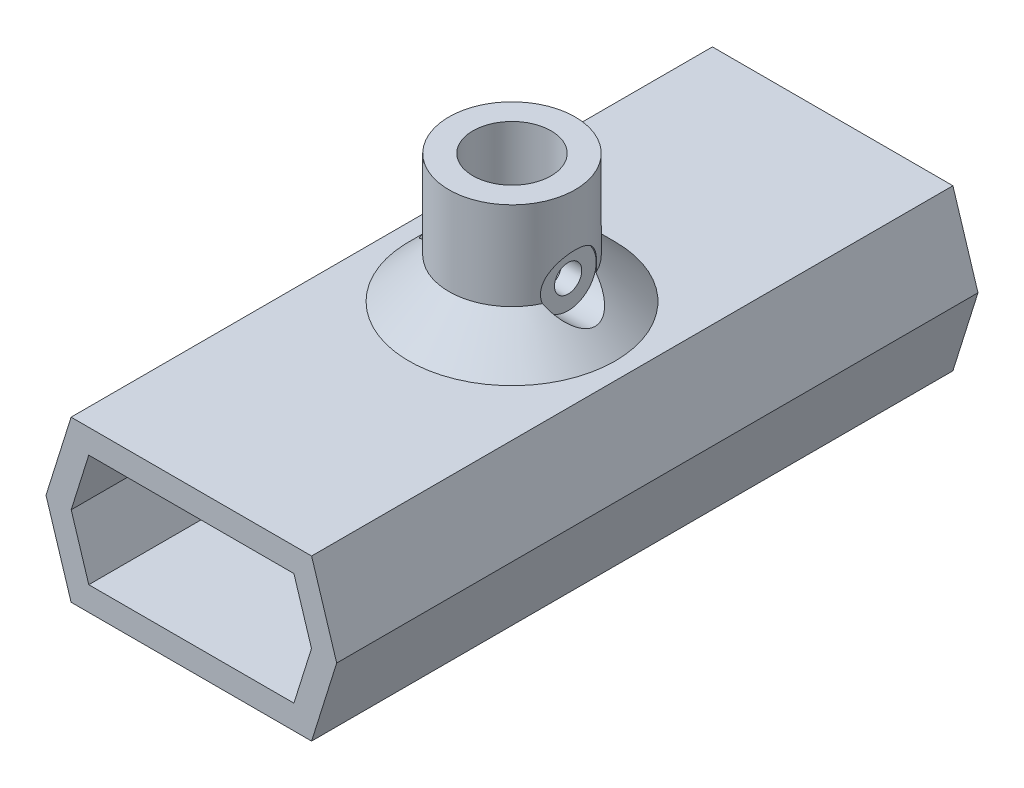
SolidWorks part; units mm, degrees
ref_plane "前视基准面" through (0, 0, 0) normal (0, 0, 1) x (1, 0, 0)
ref_plane "上视基准面" through (0, 0, 0) normal (0, 1, 0) x (1, 0, 0)
ref_plane "右视基准面" through (0, 0, 0) normal (1, 0, 0) x (0, 0, -1)
sketch "草图1" plane through (0, 0, 0) normal (0, 0, 1) x (1, 0, 0)
  line L0 (-15, 0) -> (15, 0)
  line L1 (15, 0) -> (18.1304, -10)
  line L2 (18.1304, -10) -> (15, -20)
  line L3 (15, -20) -> (-15, -20)
  line L4 (-15, -20) -> (-18.1304, -10)
  line L5 (-18.1304, -10) -> (-15, 0)
  point P6 (0, 0)
  point P9 (0, -20)
  dimension "D1" = 30
  dimension "D2" = 20
extrude "凸台-拉伸1" add sketch "草图1" along normal mid plane 80
sketch "草图7" plane through (0, 0, -40) normal (0, 0, -1) x (-1, 0, 0)
  line L12 (14.9869, -10) -> (12.7956, -3)
  line L13 (12.7956, -3) -> (-12.7956, -3)
  line L14 (-12.7956, -3) -> (-14.9869, -10)
  line L15 (-14.9869, -10) -> (-12.7956, -17)
  line L16 (-12.7956, -17) -> (12.7956, -17)
  line L17 (12.7956, -17) -> (14.9869, -10)
  line L18 (14.9869, -10) -> (12.7956, -3)
  line L19 (12.7956, -3) -> (-12.7956, -3)
  line L20 (-12.7956, -3) -> (-14.9869, -10)
  line L21 (-14.9869, -10) -> (-12.7956, -17)
  line L22 (-12.7956, -17) -> (12.7956, -17)
  line L23 (12.7956, -17) -> (14.9869, -10)
  dimension "D1" = 3
extrude "切除-拉伸3" cut sketch "草图7" against normal through all
sketch "草图3" plane through (0, 0, 0) normal (0, 0, 1) x (1, 0, 0)
  line L0 (0, 0) -> (0, 40) construction
  line L6 (15, 0) -> (-15, 0) construction
  line L7 (4.875, 16) -> (7.875, 16)
  line L8 (7.875, 16) -> (7.875, 0)
  line L10 (7.875, 0) -> (0, 0)
  line L12 (4.875, 16) -> (4.875, 2)
  line L13 (4.875, 2) -> (0, 2)
  line L14 (0, 2) -> (0, 0)
  line L15 (-15, -20) -> (15, -20) construction
  dimension "D1" = 22
  dimension "D2" = 3
  dimension "D3" = 14
  dimension "D4" = 9.75
revolve "旋转1" add sketch "草图3" angle 360 about L0
chamfer "倒角1" distance 5 angle 45 1 edges at (0, 0, -7.875)
sketch "草图5" plane through (0, 0, 0) normal (1, 0, 0) x (0, 0, -1)
  line L0 (0, 6) -> (0, 0) construction
  line L1 (4.875, 2) -> (-4.875, 2) construction
  circle A0 centre (0, 6) radius 1.7
  dimension "D1" = 3.4
  dimension "D2" = 4
extrude "切除-拉伸1" cut sketch "草图5" against normal blind 10 and the other way blind 10
ref_plane "基准面1" through (7, 0, 0) normal (1, 0, 0) x (0, 0, -1)
sketch "草图6" plane through (7, 0, 0) normal (1, 0, 0) x (0, 0, -1)
  circle A0 centre (0, 6) radius 3.5
  dimension "D1" = 7
extrude "切除-拉伸2" cut sketch "草图6" along normal blind 10
mirror "镜向1" about plane through (0, 0, 0) normal (1, 0, 0) of "切除-拉伸2"
sketch "草图8" plane through (0, -20, 0) normal (0, -1, 0) x (1, 0, 0)
  line L0 (-0.3, 0) -> (-0.3, -9.4883)
  line L1 (-0.3, -9.4883) -> (-0.9, -9.4883)
  line L5 (0, -10.3998) -> (0, 0) construction
  line L6 (0.3, 0) -> (-0.3, 0)
  line L7 (-0.9, -9.4883) -> (0, -10.3998)
  line L8 (0.9, -9.4883) -> (0, -10.3998)
  line L9 (0.3, -9.4883) -> (0.9, -9.4883)
  line L10 (0.3, 0) -> (0.3, -9.4883)
  line L11 (0, -0.3) -> (9.4883, -0.3)
  line L12 (9.4883, -0.3) -> (9.4883, -0.9)
  line L13 (0, 0.3) -> (0, -0.3)
  line L14 (9.4883, -0.9) -> (10.3998, 0)
  line L15 (9.4883, 0.9) -> (10.3998, 0)
  line L16 (9.4883, 0.3) -> (9.4883, 0.9)
  line L17 (0, 0.3) -> (9.4883, 0.3)
  line L18 (10.3998, 0) -> (0, 0) construction
  point P19 (0, 0)
  dimension "D1" = 0.3
  dimension "D2" = 0.6
  dimension "D3" = 2
extrude "切除-拉伸4" cut sketch "草图8" against normal blind 0.6 contours L14 L15 L16 L17 L13 L11 L12 | L10 L9 L8 L7 L1 L0 L6
sketch "草图9" plane through (0, -20, 0) normal (0, -1, 0) x (1, 0, 0)
  text T0 "<r90>X</r></r>" font "黑体" height 2
  text T1 "<r270>Y</r>" font "黑体" height 2
extrude "切除-拉伸5" cut sketch "草图9" against normal blind 0.6
sketch "草图10" plane through (0, 2, 0) normal (0, 1, 0) x (1, 0, 0)
  circle A0 centre (0, 0) radius 0.9076
extrude "切除-拉伸6" cut sketch "草图10" against normal blind 1
